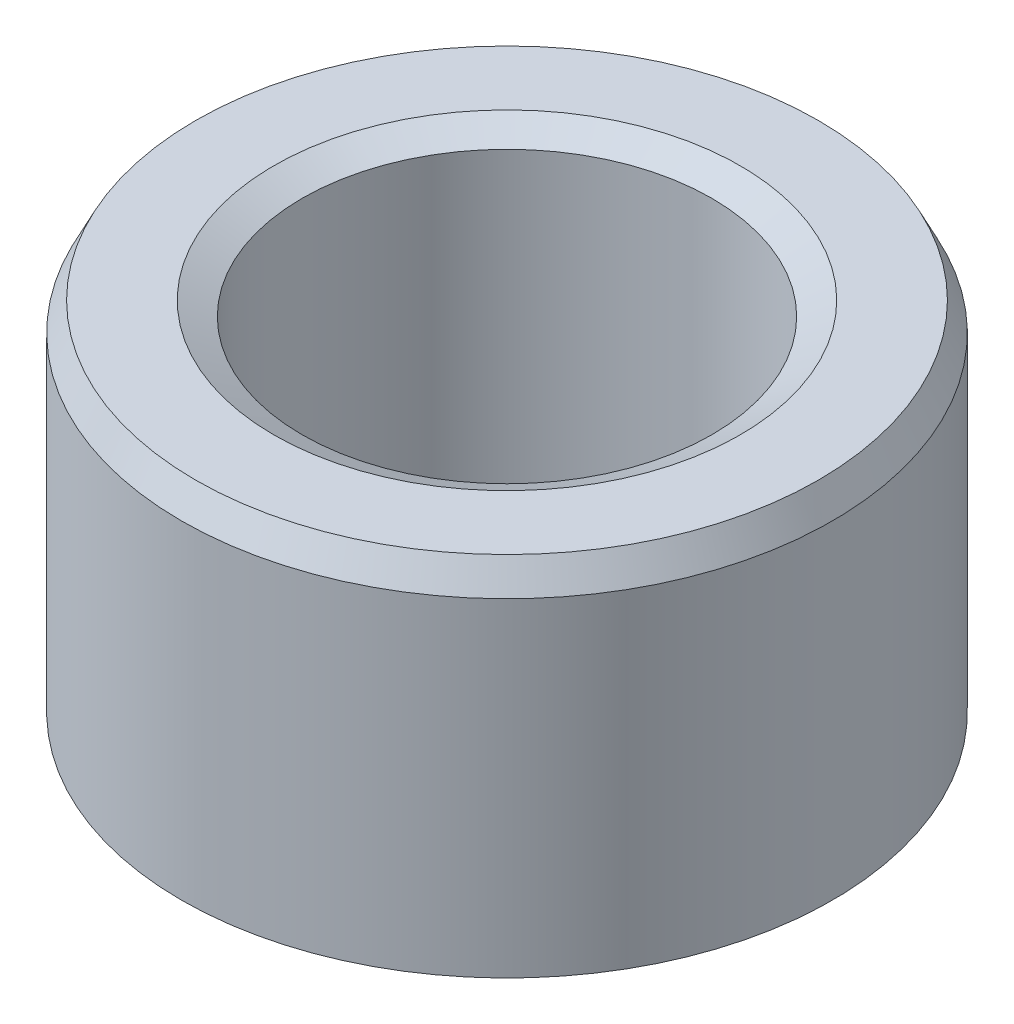
SolidWorks part; units mm, degrees
ref_plane "Front Plane" through (0, 0, 0) normal (0, 0, 1) x (1, 0, 0)
ref_plane "Top Plane" through (0, 0, 0) normal (0, 1, 0) x (1, 0, 0)
ref_plane "Right Plane" through (0, 0, 0) normal (1, 0, 0) x (0, 0, -1)
sketch "Sketch1" plane through (0, 0, 0) normal (0, 1, 0) x (1, 0, 0)
  circle A0 centre (0, 0) radius 10
  dimension "SLEEVE_OD" = 20
extrude "Boss-Extrude1" add sketch "Sketch1" along normal blind 11.3932
sketch "Sketch2" plane through (0, 0, 0) normal (0, 1, 0) x (1, 0, 0)
  circle A0 centre (0, 0) radius 6.2932
  dimension "BORE_D" = 12.5863
extrude "Cut-Extrude1" cut sketch "Sketch2" along normal through all
chamfer "Chamfer1" distance 0.8703 angle 26.405 4 edges at (0, 11.3932, 6.2932) (0, 0, 6.2932) (0, 0, 10) (0, 11.3932, 10) first distance on face at (0, 11.3932, 6.2932) first distance on face at (0, 0, 6.2932) first distance on face at (0, 11.3932, 10)
